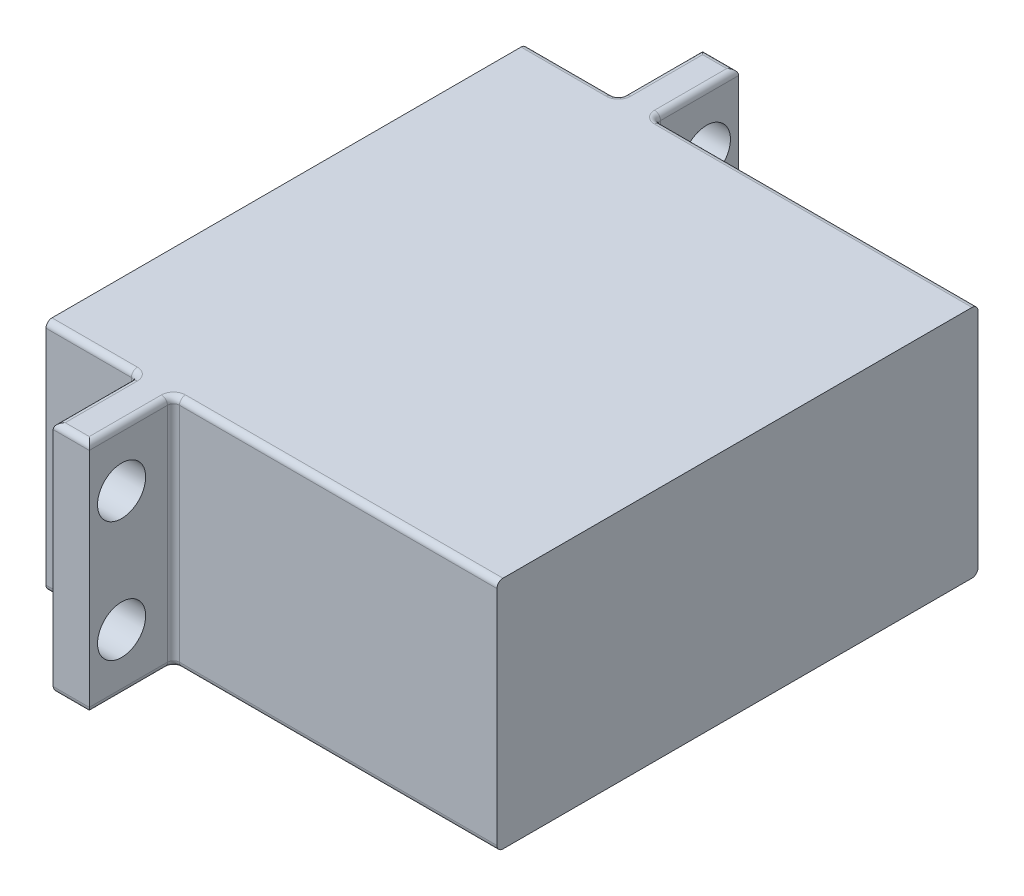
SolidWorks part; units mm, degrees
ref_plane "前视基准面" through (0, 0, 0) normal (0, 0, 1) x (1, 0, 0)
ref_plane "上视基准面" through (0, 0, 0) normal (0, 1, 0) x (1, 0, 0)
ref_plane "右视基准面" through (0, 0, 0) normal (1, 0, 0) x (0, 0, -1)
sketch "草图1" plane through (0, 0, 0) normal (0, 0, 1) x (1, 0, 0)
  line L1 (-45.8462, 44.1538) -> (-8.3462, 44.1538)
  line L2 (-45.8462, 44.1538) -> (-45.8462, 24.6538)
  line L3 (-45.8462, 24.6538) -> (-8.3462, 24.6538)
  line L4 (-8.3462, 44.1538) -> (-8.3462, 24.6538)
  dimension "D1" = 37.5
  dimension "D2" = 19.5
extrude "凸台-拉伸1" add sketch "草图1" along normal blind 40 contours L1 L4 L3 L2
ref_plane "基准面4" through (-35.2462, 0, 0) normal (-1, 0, 0) x (0, 0, 1)
sketch "草图2" plane through (-35.2462, 0, 0) normal (-1, 0, 0) x (0, 0, 1)
  line L0 (0, 24.6538) -> (50000, 24.6538) construction
  line L8 (0, 44.1538) -> (-7, 44.1538)
  line L9 (0, 44.1538) -> (0, 24.6538)
  line L10 (0, 24.6538) -> (-7, 24.6538)
  line L11 (-7, 44.1538) -> (-7, 24.6538)
  line L12 (40, 44.1538) -> (47, 44.1538)
  line L13 (40, 44.1538) -> (40, 24.6538)
  line L14 (40, 24.6538) -> (47, 24.6538)
  line L15 (47, 44.1538) -> (47, 24.6538)
  dimension "D1" = 54
extrude "凸台-拉伸2" add sketch "草图2" along normal blind 3
sketch "草图3" plane through (-35.2462, 0, 0) normal (-1, 0, 0) x (0, 0, 1)
  line L0 (0, 24.6538) -> (40, 24.6538) construction
  line L3 (20, 24.6538) -> (20, 45.208) construction
  line L6 (-7, 24.6538) -> (0, 24.6538) construction
  line L7 (-7, 33.9033) -> (40, 34.4038) construction
  line L8 (-7, 44.1538) -> (-7, 24.6538) construction
  line L11 (40, 44.1538) -> (40, 24.6538) construction
  circle A0 centre (-4.315, 39.4038) radius 2
  circle A1 centre (-4.315, 29.4038) radius 2
  dimension "D1" = 4
  dimension "D5" = 4
  dimension "D2" = 10
  dimension "D3" = 24.315
  dimension "D4" = 4.75
extrude "切除-拉伸5" cut sketch "草图3" against normal through all and the other way blind 3 contours A1 | A0 region at (-35.2462, 39.4038, -4.315) region at (-35.2462, 29.4038, -4.315)
sketch "草图4" plane through (-45.8462, 0, 0) normal (-1, 0, 0) x (0, 0, 1)
  line L0 (0, 34.4038) -> (40, 34.4038) construction
  line L1 (0, 44.1538) -> (0, 24.6538) construction
  line L2 (40, 44.1538) -> (40, 24.6538) construction
  line L3 (40, 44.1538) -> (40, 24.6538) construction
  circle A1 centre (30, 34.4038) radius 2.45
  dimension "D1" = 10
  dimension "D2" = 4.9
extrude "凸台-拉伸3" add sketch "草图4" along normal blind 4
fillet "圆角1" radius 0.5 25 edges at (-42.0462, 44.1538, 40) (-42.0462, 24.6538, 40) (-42.0462, 24.6538, 0) (-42.0462, 44.1538, 0) (-49.8462, 31.9538, 30) (-35.2462, 34.4038, 40) (-35.2462, 24.6538, 43.5) (-35.2462, 44.1538, 43.5) (-38.2462, 34.4038, 40) (-38.2462, 24.6538, 43.5) (-38.2462, 44.1538, 43.5) (-36.7462, 44.1538, 47) (-35.2462, 34.4038, 0) (-35.2462, 44.1538, -3.5) (-35.2462, 24.6538, -3.5) (-38.2462, 34.4038, 0) (-38.2462, 44.1538, -3.5) (-38.2462, 24.6538, -3.5) (-36.7462, 24.6538, -7) (-36.7462, 44.1538, -7) (-36.7462, 24.6538, 47) (-21.7962, 24.6538, 0) (-21.7962, 44.1538, 40) (-21.7962, 44.1538, 0) (-21.7962, 24.6538, 40)
ref_plane "基准面5" through (0, 0, 20) normal (0, 0, -1) x (-1, 0, 0)
mirror "镜向1" about plane through (0, 0, 20) normal (0, 0, -1) of "切除-拉伸5"
